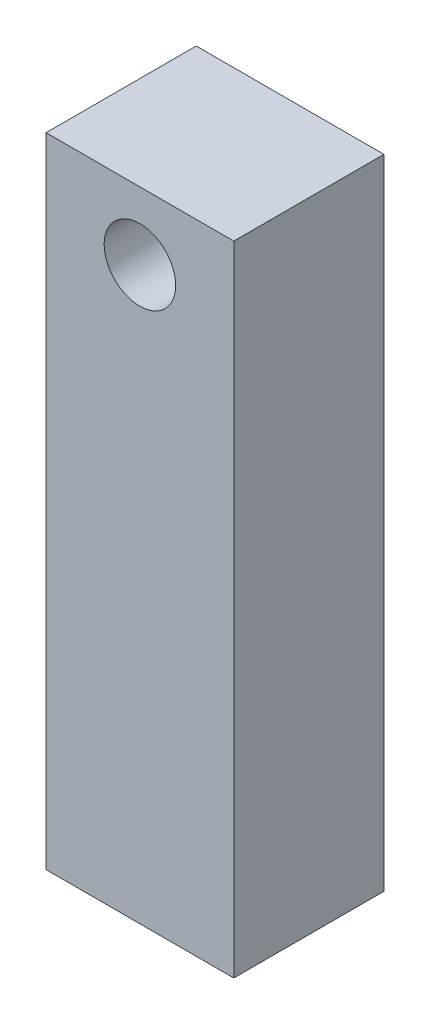
SolidWorks part; units mm, degrees
material "Plain Carbon Steel"
ref_plane "Front Plane" through (0, 0, 0) normal (0, 0, 1) x (1, 0, 0)
ref_plane "Top Plane" through (0, 0, 0) normal (0, 1, 0) x (1, 0, 0)
ref_plane "Right Plane" through (0, 0, 0) normal (1, 0, 0) x (0, 0, -1)
sketch "Sketch1" plane through (0, 0, 0) normal (0, 1, 0) x (1, 0, 0)
  line L0 (-12.5, -10) -> (12.5, -10)
  line L1 (12.5, -10) -> (12.5, 10)
  line L2 (12.5, 10) -> (-12.5, 10)
  line L3 (-12.5, 10) -> (-12.5, -10)
  dimension "D1" = 25
  dimension "D2" = 20
  dimension "D3" = 12.5
  dimension "D4" = 10
extrude "Boss-Extrude1" add sketch "Sketch1" along normal blind 85
sketch "Sketch2" plane through (0, 0, 0) normal (0, 0, 1) x (1, 0, 0)
  circle A0 centre (0, 76) radius 4.7625
  dimension "D2" = 9.525
  dimension "D1" = 76
extrude "Cut-Extrude1" cut sketch "Sketch2" against normal mid plane 24
